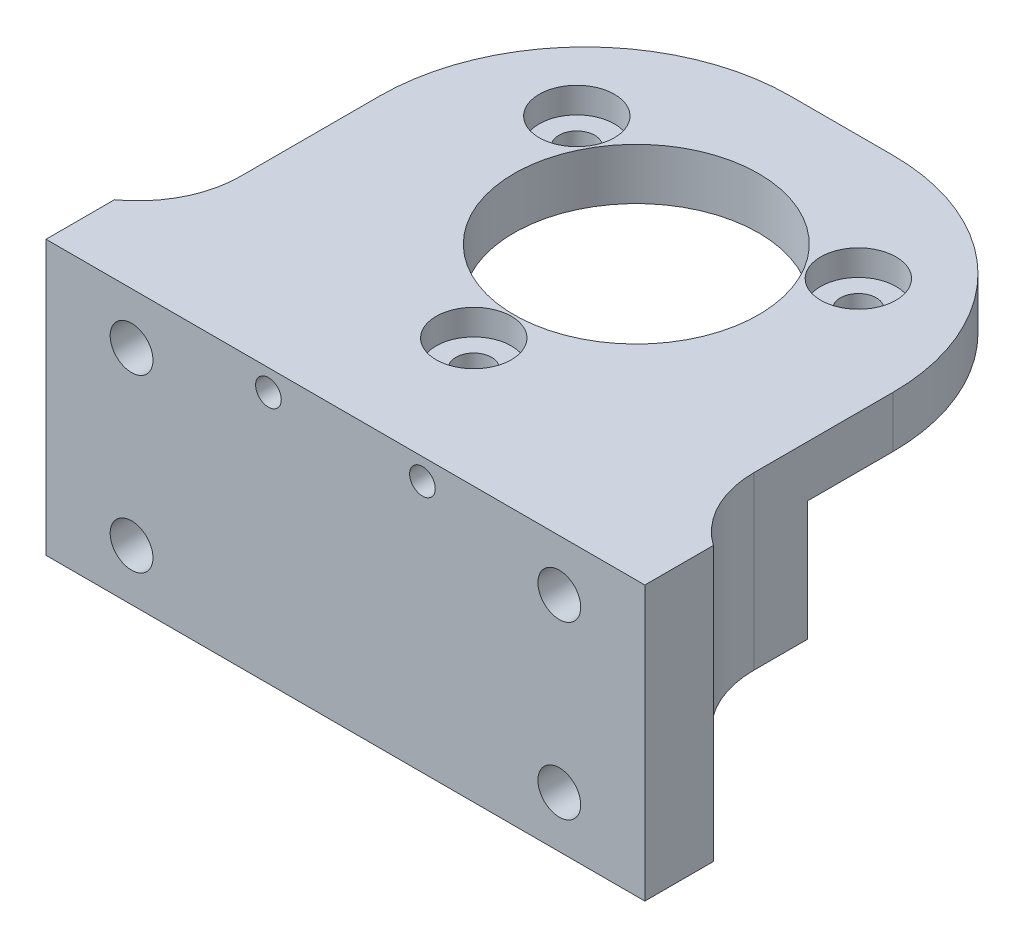
SolidWorks part; units mm, degrees
ref_plane "Front Plane" through (0, 0, 0) normal (0, 0, 1) x (1, 0, 0)
ref_plane "Top Plane" through (0, 0, 0) normal (0, 1, 0) x (1, 0, 0)
ref_plane "Right Plane" through (0, 0, 0) normal (1, 0, 0) x (0, 0, -1)
sketch "Sketch1" plane through (0, 0, 0) normal (0, 0, 1) x (1, 0, 0)
  line L1 (-15, -5) -> (15, -5)
  line L2 (-15, -5) -> (-15, 5)
  line L3 (-15, 5) -> (15, 5)
  line L4 (15, -5) -> (15, 5)
  line L5 (-15, -5) -> (15, 5) construction
  line L6 (-15, 5) -> (15, -5) construction
  point P0 (0, 0)
  point P11 (0, 0)
  point P13 (0, 0.5)
  dimension "D1" = 30
  dimension "D2" = 10
extrude "Main" add sketch "Sketch1" along normal blind 25
sketch "Sketch5" plane through (0, -5, 0) normal (0, -1, 0) x (-1, 0, 0)
  line L0 (0, -21.5) -> (-8.2272, -7.25) construction
  line L1 (-8.2272, -7.25) -> (8.2272, -7.25) construction
  line L2 (8.2272, -7.25) -> (0, -21.5) construction
  line L4 (15, 0) -> (-15, 0) construction
  circle A0 centre (0, -12) radius 9.5 construction
  circle A1 centre (0, -21.5) radius 1.05
  circle A2 centre (-8.2272, -7.25) radius 1.05
  circle A3 centre (8.2272, -7.25) radius 1.05
  circle A4 centre (0, -12) radius 7.15
  dimension "D1" = 19
  dimension "D2" = 2.1
  dimension "D4" = 14.3
  dimension "D3" = 12
extrude "MainAndFixHole" cut sketch "Sketch5" against normal through all
sketch "Sketch6" plane through (0, 5, 0) normal (0, -1, 0) x (-1, 0, 0)
  circle A0 centre (0, -21.5) radius 2.2
  circle A1 centre (-8.2272, -7.25) radius 2.2
  circle A2 centre (8.2272, -7.25) radius 2.2
  dimension "D1" = 4.4
extrude "CoderFixHole2" cut sketch "Sketch6" along normal blind 1.5
sketch "Sketch11" plane through (0, -5, 0) normal (0, 1, 0) x (1, 0, 0)
  line L0 (-15, 0) -> (15, 0)
  line L1 (15, 0) -> (15, -17)
  line L2 (15, -17) -> (10.9087, -17)
  line L3 (-15, 0) -> (-15, -17)
  line L4 (-15, -17) -> (-10.9087, -17)
  line L8 (-15, 0) -> (15, 0) construction
  line L9 (15, -25) -> (15, 0) construction
  arc A0 (10.9087, -17) -> (-10.9087, -17) centre (0, -12) cw
  circle A1 centre (0, -12) radius 7.15 construction
  dimension "D1" = 12
  dimension "D2" = 5
extrude "CoderHole2" cut sketch "Sketch11" along normal blind 7
sketch "Sketch10" plane through (0, 0, 25) normal (0, 0, 1) x (1, 0, 0)
  line L0 (-15, -5) -> (15, -5) construction
  line L1 (-17.5, -11) -> (17.5, -11)
  line L2 (-17.5, -11) -> (-17.5, 5)
  line L3 (-17.5, 5) -> (17.5, 5)
  line L4 (17.5, -11) -> (17.5, 5)
  line L5 (15, 5) -> (-15, 5) construction
  point P4 (0, -5)
  point P5 (0, -5)
  point P11 (0, 5)
  dimension "D1" = 16
  dimension "D2" = 35
extrude "Link" add sketch "Sketch10" along normal blind 4
sketch "Sketch8" plane through (0, 0, 29) normal (0, 0, 1) x (1, 0, 0)
  line L0 (17.5, -11) -> (17.5, 5) construction
  line L2 (15, 5) -> (-15, 5) construction
  line L5 (17.5, 5) -> (-17.5, 5) construction
  circle A0 centre (12.5, 2) radius 1.25
  point P3 (17.5, -3)
  point P11 (0, 5)
  dimension "D3" = 2.5
  dimension "D1" = 3
  dimension "D2" = 12.5
  dimension "D4" = 8
extrude "VerticalHoles" cut sketch "Sketch8" against normal up to surface (12 mm away) up to face at (-12.9544, -1.5, 17)
sketch "Sketch13" plane through (0, 0, 25) normal (0, 0, -1) x (-1, 0, 0)
  line L2 (-17.5, -11) -> (-17.5, 5) construction
  line L3 (-12.5, -8) -> (12.5, -8) construction
  circle A0 centre (-12.5, -8) radius 2.5
  circle A1 centre (12.5, -8) radius 2.5
  arc A2 (-13.75, 2) -> (-11.25, 2) centre (-12.5, 2) ccw construction
  point P2 (0, -8)
  dimension "D3" = 5
  dimension "D1" = 10
  dimension "D2" = 5
extrude "LinkReinforcement" add sketch "Sketch13" along normal blind 2
fillet "Fillet4" radius 6 2 edges at (15, 0, 25) (-15, 0, 25)
fillet "Fillet6" radius 12 2 edges at (15, 3.5, 0) (-15, 3.5, 0)
pattern_linear "HoleLPattern1" count 2 spacing 25 along (-1, 0, 0) count 2 spacing 10 along (0, -1, 0) of "VerticalHoles"
sketch "Sketch14" plane through (0, 0, 29) normal (0, 0, 1) x (1, 0, 0)
  line L0 (-4.5, 3.75) -> (4.5, 3.75) construction
  line L1 (17.5, 5) -> (-17.5, 5) construction
  circle A0 centre (4.5, 3.75) radius 0.75
  circle A1 centre (-4.5, 3.75) radius 0.75
  point P5 (0, 3.75)
  dimension "D1" = 1.5
  dimension "D2" = 1.25
  dimension "D3" = 4.5
extrude "HoleToAccessEncoderScrew" cut sketch "Sketch14" against normal up to surface (12.1461 mm away) up to face at (0, 5, 4.85)
